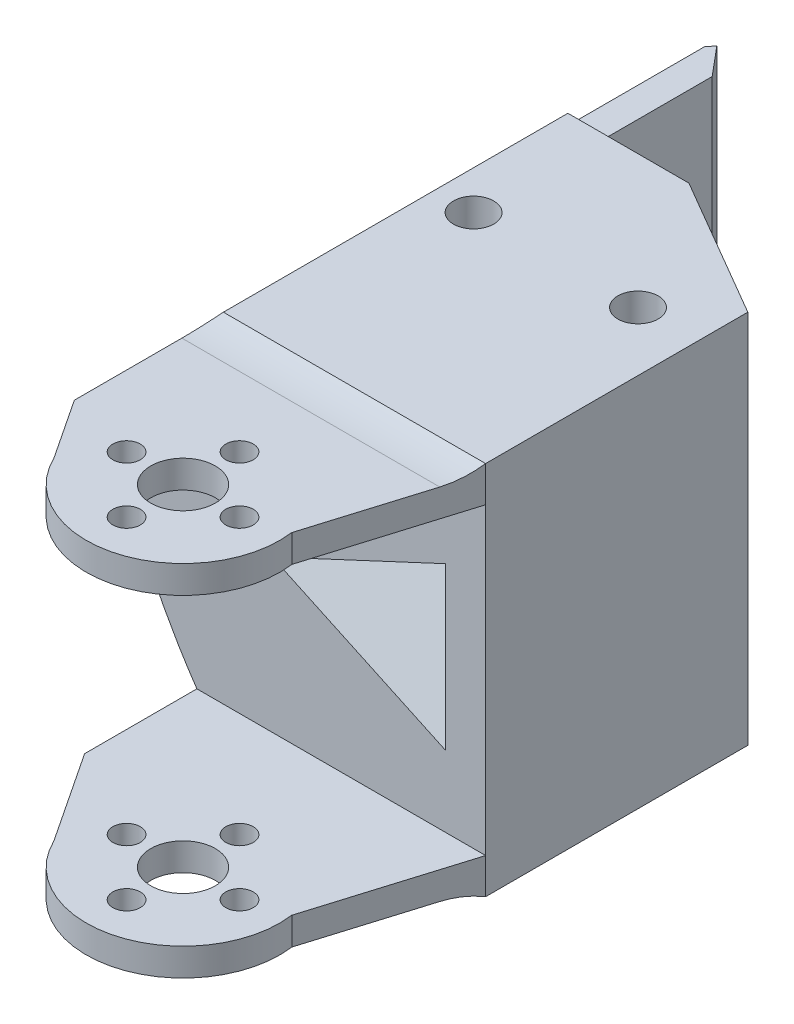
SolidWorks part; units mm, degrees
ref_plane "Front Plane" through (0, 0, 0) normal (0, 0, 1) x (1, 0, 0)
ref_plane "Top Plane" through (0, 0, 0) normal (0, 1, 0) x (1, 0, 0)
ref_plane "Right Plane" through (0, 0, 0) normal (1, 0, 0) x (0, 0, -1)
sketch "Sketch2" plane through (0, 0, 0) normal (0, 1, 0) x (1, 0, 0)
  line L0 (17.5, 0) -> (17.5, 37.7)
  line L1 (-15, 2.5) -> (15, 2.5)
  line L2 (-15, 2.5) -> (-15, 37.7)
  line L4 (15, 2.5) -> (15, 37.7)
  line L5 (17.5, 37.7) -> (15, 37.7)
  line L7 (-17.5, 37.7) -> (-17.5, 0)
  line L8 (-17.5, 0) -> (17.5, 0)
  line L10 (-17.5, 37.7) -> (-15, 37.7)
  point P4 (0, 2.5)
  point P12 (0, 0)
  dimension "D1" = 2.5
  dimension "D2" = 2.5
  dimension "D3" = 37.7
  dimension "D4" = 30
  dimension "D5" = 15
extrude "Boss-Extrude1" add sketch "Sketch2" along normal blind 32.5
sketch "Sketch4" plane through (0, 0, 0) normal (0, -1, 0) x (1, 0, 0)
  line L0 (-17.5, 0) -> (-17.5, -7.4438)
  line L8 (17.5, -7.4438) -> (17.5, 0)
  line L9 (17.5, 0) -> (-17.5, 0)
  line L10 (17.5, 0) -> (17.5, -37.7) construction
  line L13 (-17.5, -7.4438) -> (-17.5, -37.7)
  line L23 (-17.5, -37.7) -> (-15, -37.7)
  line L34 (-15, -37.7) -> (-15, -7.5)
  line L35 (-15, -2.5) -> (-15, -37.7) construction
  line L36 (-15, -7.5) -> (15, -7.5)
  line L37 (15, -37.7) -> (15, -2.5) construction
  line L38 (15, -7.5) -> (15, -37.7)
  line L39 (15, -37.7) -> (17.5, -37.7)
  line L40 (17.5, -37.7) -> (17.5, -7.4438)
  circle A2 centre (-10.1889, -4.95) radius 1.05
  circle A5 centre (10.1889, -4.95) radius 1.05
  dimension "D5" = 2.1
  dimension "D1" = 7.5
  dimension "D6" = 7.3111
  dimension "D7" = 4.95
  dimension "D8" = 7.3111
extrude "Boss-Extrude2" add sketch "Sketch4" along normal blind 2
sketch "Sketch7" plane through (0, -2, 0) normal (0, -1, 0) x (1, 0, 0)
  line L0 (-17.5, 0) -> (-17.5, -37.7)
  line L1 (-17.5, -37.7) -> (-15, -37.7)
  line L2 (-17.5, 0) -> (17.5, 0)
  line L4 (17.5, 0) -> (17.5, -37.7)
  line L5 (17.5, -37.7) -> (15, -37.7)
  line L6 (15, -37.7) -> (15, -7.5)
  line L7 (15, -7.5) -> (-15, -7.5)
  line L8 (-15, -7.5) -> (-15, -37.7)
  circle A2 centre (-10.1889, -4.95) radius 2.495
  circle A3 centre (10.1889, -4.95) radius 2.495
  dimension "D1" = 4.99
extrude "Wire spacing2" add sketch "Sketch7" along normal blind 3
sketch "Sketch8" plane through (0, -5, 0) normal (0, -1, 0) x (1, 0, 0)
  line L0 (-17.5, 0) -> (-17.5, -37.7)
  line L1 (-17.5, -37.7) -> (17.5, -37.7)
  line L2 (17.5, -37.7) -> (17.5, 0) construction
  line L3 (15, -37.7) -> (17.5, -37.7) construction
  line L4 (-17.5, 0) -> (17.5, 0)
  line L6 (17.5, 0) -> (17.5, -37.7)
  circle A0 centre (-10.1889, -4.95) radius 2.495
  circle A1 centre (10.1889, -4.95) radius 2.495
  circle A2 centre (10.1889, -4.95) radius 2.495 construction
  circle A3 centre (-10.1889, -4.95) radius 2.495 construction
extrude "Boss-Extrude6" add sketch "Sketch8" along normal blind 2
sketch "Sketch5" plane through (0, 32.5, 0) normal (0, 1, 0) x (1, 0, 0)
  line L0 (-7.439, 10) -> (-7.439, 2.5)
  line L9 (15, 2.5) -> (-15, 2.5) construction
  line L11 (-10.1889, 12) -> (-7.439, 10)
  line L13 (-17.5, 0) -> (17.5, 0) construction
  line L15 (-17.5, 0) -> (-17.5, 37.7)
  line L17 (10.1889, 12) -> (7.439, 10)
  line L20 (17.5, 0) -> (17.5, 37.7)
  line L21 (-7.439, 2.5) -> (7.439, 2.5)
  line L22 (7.439, 2.5) -> (7.439, 10)
  line L23 (-17.5, 0) -> (17.5, 0)
  line L24 (-10.1889, 12) -> (-15, 12)
  line L25 (-15, 37.7) -> (-15, 7.5) construction
  line L26 (-15, 12) -> (-15, 37.7)
  line L27 (-15, 37.7) -> (-17.5, 37.7)
  line L30 (17.5, 37.7) -> (15, 37.7)
  line L31 (15, 37.7) -> (15, 12)
  line L32 (15, 7.5) -> (15, 37.7) construction
  line L33 (15, 12) -> (10.1889, 12)
  circle A0 centre (-10.1889, 4.95) radius 1.05 construction
  circle A1 centre (-10.1889, 8.7) radius 1.05
  circle A2 centre (10.1889, 8.7) radius 1.05
  circle A3 centre (10.1889, 4.95) radius 1.05 construction
  dimension "D4" = 0
  dimension "D7" = 8.7
  dimension "D3" = 0
  dimension "D1" = 12
  dimension "D2" = 10.061
  dimension "D5" = 10
  dimension "D6" = 10.061
extrude "Boss-Extrude3" add sketch "Sketch5" along normal blind 2
sketch "Sketch9" plane through (0, 34.5, 0) normal (0, 1, 0) x (1, 0, 0)
  line L0 (-17.5, 0) -> (-17.5, 37.7)
  line L1 (-17.5, 37.7) -> (-15, 37.7)
  line L2 (-15, 37.7) -> (-15, 12)
  line L3 (-15, 12) -> (-10.1889, 12)
  line L4 (-10.1889, 12) -> (-7.439, 10)
  line L5 (-7.439, 10) -> (-7.439, 2.5)
  line L6 (-7.439, 2.5) -> (7.439, 2.5)
  line L7 (7.439, 2.5) -> (7.439, 10)
  line L8 (7.439, 10) -> (10.1889, 12)
  line L9 (10.1889, 12) -> (7.439, 10) construction
  line L10 (10.1889, 12) -> (15, 12)
  line L11 (15, 7.5) -> (15, 37.7) construction
  line L12 (15, 12) -> (15, 37.7)
  line L13 (15, 37.7) -> (17.5, 37.7)
  line L14 (17.5, 0) -> (17.5, 37.7) construction
  line L15 (17.5, 37.7) -> (15, 37.7) construction
  line L16 (17.5, 37.7) -> (17.5, 0)
  line L17 (17.5, 0) -> (-17.5, 0)
  line L18 (15, 12) -> (10.1889, 12) construction
  circle A0 centre (-10.1889, 8.7) radius 2.495
  circle A1 centre (10.1889, 8.7) radius 2.495
  dimension "D1" = 4.99
  dimension "D2" = 0
extrude "Wire spacing1" add sketch "Sketch9" along normal blind 3
sketch "Sketch10" plane through (0, 37.5, 0) normal (0, 1, 0) x (1, 0, 0)
  line L1 (-17.5, 37.7) -> (17.5, 37.7)
  line L2 (-17.5, 37.7) -> (-17.5, 0)
  line L3 (-17.5, 0) -> (17.5, 0)
  line L4 (17.5, 37.7) -> (17.5, 0)
  circle A0 centre (-10.1889, 8.7) radius 2.495
  circle A1 centre (10.1889, 8.7) radius 2.495
  circle A2 centre (-10.1889, 8.7) radius 2.495 construction
  circle A3 centre (10.1889, 8.7) radius 2.495 construction
extrude "Boss-Extrude8" add sketch "Sketch10" along normal blind 2
sketch "Sketch11" plane through (0, 39.5, 0) normal (0, 1, 0) x (1, 0, 0)
  line L0 (17.5, 37.7) -> (-17.5, 37.7) construction
  circle A0 centre (0, 37.7) radius 12.5
  dimension "D1" = 25
extrude "Cut-Extrude1" cut sketch "Sketch11" against normal through all
sketch "Sketch12" plane through (0, -7, 0) normal (0, -1, 0) x (1, 0, 0)
  line L4 (0, -25.2) -> (17.5, -15)
  line L5 (17.5, -37.7) -> (17.5, 0) construction
  line L6 (17.5, -15) -> (17.5, -47.4845)
  line L7 (17.5, -47.4845) -> (0, -25.2)
  line L8 (17.5, 0) -> (-17.5, 0) construction
  arc A1 (12.5, -37.7) -> (-12.5, -37.7) centre (0, -37.7) ccw construction
  dimension "D1" = 15
extrude "Cut-Extrude2" cut sketch "Sketch12" against normal through all
sketch "Sketch13" plane through (0, 0, 0) normal (0, 0, 1) x (1, 0, 0)
  line L0 (17.5, -7) -> (-17.5, -7) construction
  line L1 (17.5, 39.5) -> (-27.5, 39.5)
  line L2 (17.5, 39.5) -> (17.5, -7)
  line L3 (17.5, -7) -> (-27.5, -7)
  line L4 (-27.5, 39.5) -> (-27.5, -7)
  line L5 (-17.5, 39.5) -> (-17.5, -7) construction
  dimension "D1" = 10
extrude "Boss-Extrude9" add sketch "Sketch13" along normal blind 17.5
sketch "Sketch15" plane through (0, 0, 0) normal (0, 0, -1) x (-1, 0, 0)
  line L0 (17.5, -7) -> (12.5, -7) construction
  line L1 (27.5, 39.5) -> (15, 39.5)
  line L2 (27.5, 39.5) -> (27.5, -7)
  line L3 (27.5, -7) -> (15, -7)
  line L4 (15, 39.5) -> (15, -7)
extrude "Boss-Extrude10" add sketch "Sketch15" along normal blind 50
sketch "Sketch18" plane through (0, -7, 0) normal (0, -1, 0) x (1, 0, 0)
  line L0 (12.5, 22.5) -> (12.5, 17.5)
  line L1 (12.5, 17.5) -> (-12.5, 17.5)
  line L2 (-12.5, 22.5) -> (-12.5, 17.5)
  line L3 (12.5, 22.5) -> (9.3675, 30)
  line L4 (-9.3675, 30) -> (-12.5, 22.5)
  line L5 (-27.5, 17.5) -> (17.5, 17.5) construction
  circle A0 centre (0, 37.5) radius 4
  arc A1 (9.3675, 30) -> (-9.3675, 30) centre (0, 37.5) ccw
  circle A2 centre (0, 30.5) radius 1.7
  circle A3 centre (-7, 37.5) radius 1.7
  circle A4 centre (0, 44.5) radius 1.7
  circle A5 centre (7, 37.5) radius 1.7
  point P11 (7.7726, 26.3901)
  point P12 (0, 17.5)
  point P21 (0, 49.5)
  dimension "D3" = 8
  dimension "D5" = 12
  dimension "D7" = 3.4
  dimension "D1" = 25
  dimension "D2" = 20
  dimension "D4" = 5
  dimension "D6" = 12.5
  dimension "D8" = 7
  dimension "D9" = 7
  dimension "D10" = 7
  dimension "D11" = 7
  dimension "D12" = 0
  dimension "D13" = 0
extrude "Boss-Extrude11" add sketch "Sketch18" against normal up to surface (46.5 mm away) up to face at (-8.1361, 39.5, -22.2514)
sketch "Sketch22" plane through (0, -7, 0) normal (0, -1, 0) x (1, 0, 0)
  line L0 (-27.5, 17.5) -> (-9, 45.4373)
  line L1 (-9, 45.4373) -> (-9, 17.5)
  line L2 (-9, 17.5) -> (-27.5, 17.5)
  line L4 (17.5, 17.5) -> (9, 45.4373)
  line L5 (9, 45.4373) -> (9, 17.5)
  line L6 (9, 17.5) -> (17.5, 17.5)
  arc A0 (9.3675, 30) -> (-9.3675, 30) centre (0, 37.5) ccw construction
  circle A1 centre (-7, 37.5) radius 1.7 construction
  circle A2 centre (7, 37.5) radius 1.7 construction
  dimension "D1" = 2
  dimension "D2" = 2
extrude "Boss-Extrude13" add sketch "Sketch22" against normal up to surface (46.5 mm away) up to face at (-4.6492, 39.5, -1.3222)
sketch "Sketch21" plane through (-27.5, 0, 0) normal (-1, 0, 0) x (0, 0, 1)
  line L1 (107.4125, 35.075) -> (17.5, 35.075)
  line L2 (107.4125, 35.075) -> (107.4125, -2.575)
  line L3 (107.4125, -2.575) -> (17.5, -2.575)
  line L4 (17.5, 35.075) -> (17.5, -2.575)
  line L6 (-50, -7) -> (-50, 39.5) construction
  line L7 (17.5, 39.5) -> (17.5, -7) construction
  point P6 (-50, 16.25)
  point P7 (17.5, 16.25)
  dimension "D1" = 37.65
  dimension "D2" = 0
extrude "Cut-Extrude3" cut sketch "Sketch21" against normal through all
sketch "Sketch26" plane through (0, 39.5, 0) normal (0, 1, 0) x (1, 0, 0)
  line L0 (-27.5, -17.5) -> (-27.5, 50) construction
  line L1 (-27.5, 29.3872) -> (-27.5, 50)
  line L2 (-27.5, 50) -> (-15, 50)
  spline S0 degree 2 poles (-15, 50) (-23.5947, 41.1535) (-27.5, 29.3872) knots 0 0 0 1 1 1
extrude "Cut-Extrude5" cut sketch "Sketch26" against normal through all
sketch "Sketch24" plane through (0, 0, 0) normal (0, 0, -1) x (-1, 0, 0)
  line L4 (15, -7) -> (27.5, -7)
  line L5 (27.5, -7) -> (27.5, 16.25)
  spline S0 degree 2 poles (27.5, 16.25) (23.3985, 3.4824) (15, -7) knots 0 0 0 1 1 1
extrude "Cut-Extrude4" cut sketch "Sketch24" against normal through all both and the other way through all
ref_plane "Plane1" through (0, 16.25, 0) normal (0, -1, 0) x (-1, 0, 0)
mirror "Mirror1" about plane through (0, 16.25, 0) normal (0, -1, 0) of "Cut-Extrude4"
sketch "Sketch27" plane through (0, 0, -2.5) normal (0, 0, -1) x (-1, 0, 0)
  line L0 (-12.5, 26.25) -> (8.9451, 16.25)
  line L1 (-17.875, 16.25) -> (17.875, 16.25) construction
  line L2 (8.9451, 16.25) -> (-12.5, 6.25)
  line L4 (-12.5, 6.25) -> (-12.5, 26.25)
  line L5 (-15, 32.5) -> (-15, 0) construction
  point P7 (-12.5, 16.25)
  dimension "D1" = 50
  dimension "D2" = 20
  dimension "D3" = 2.5
extrude "Cut-Extrude6" cut sketch "Sketch27" against normal through all
sketch "Sketch28" plane through (0, 39.5, 0) normal (0, 1, 0) x (1, 0, 0)
  line L0 (-15, 37.7) -> (-15, 50)
  line L1 (-15, 50) -> (-10, 50)
  line L2 (-10, 50) -> (-10, 47.127)
  line L3 (-10, 47.127) -> (-12.5, 47.127)
  line L4 (-12.5, 47.127) -> (-12.5, 37.7)
  line L5 (-15, 37.7) -> (-12.5, 37.7)
  dimension "D1" = 2.5
extrude "Boss-Extrude14" add sketch "Sketch28" against normal up to surface (46.5 mm away) up to face at (-0.7656, -7, 3.6462)
fillet "Fillet2" radius 10 1 edges at (-15, 16.25, -50)
sketch "Sketch29" plane through (0, 0, -37.7) normal (0, 0, 1) x (1, 0, 0)
  line L1 (-15, 37.5) -> (-12.5, 37.5)
  line L2 (-15, 37.5) -> (-15, -5)
  line L3 (-15, -5) -> (-12.5, -5)
  line L4 (-12.5, 37.5) -> (-12.5, -5)
extrude "Cut-Extrude8" cut sketch "Sketch29" against normal up to surface (9.427 mm away) up to face at (-11.25, 16.25, -47.127)
fillet "Fillet3" radius 1 1 edges at (-10, 16.25, -47.127)
sketch "Sketch33" plane through (0, 0, -50) normal (0, 0, -1) x (-1, 0, 0)
  line L1 (0, 39.5) -> (21.955, 39.5)
  line L2 (0, 39.5) -> (0, 34.5)
  line L3 (0, 34.5) -> (21.955, 34.5)
  line L4 (21.955, 39.5) -> (21.955, 34.5)
  line L5 (0, -7) -> (23.3737, -7)
  line L6 (0, -7) -> (0, -2)
  line L7 (0, -2) -> (23.3737, -2)
  line L8 (23.3737, -7) -> (23.3737, -2)
  dimension "D1" = 5
  dimension "D2" = 5
extrude "Cut-Extrude13" cut sketch "Sketch33" against normal up to vertex (24.8 mm away) up to point (0, 39.5, -25.2)
sketch "Sketch34" plane through (0, 34.5, 0) normal (0, 1, 0) x (1, 0, 0)
  line L0 (0, 25.2) -> (-17.9905, 46.6483)
  line L1 (-17.9905, 46.6483) -> (-19.0359, 53.4266)
  line L2 (-19.0359, 53.4266) -> (0, 53.4266)
  line L3 (0, 53.4266) -> (0, 25.2)
extrude "Cut-Extrude14" cut sketch "Sketch34" against normal through all both and the other way through all
sketch "Sketch36" plane through (17.5, 0, 0) normal (1, 0, 0) x (0, 0, -1)
  line L1 (-17.5, 39.5) -> (-49.5, 39.5)
  line L2 (-17.5, 39.5) -> (-17.5, 38.5)
  line L3 (-17.5, 38.5) -> (-49.5, 38.5)
  line L4 (-49.5, 39.5) -> (-49.5, 38.5)
  line L6 (-17.5, -7) -> (-49.5, -7)
  line L7 (-17.5, -7) -> (-17.5, -6)
  line L8 (-17.5, -6) -> (-49.5, -6)
  line L9 (-49.5, -7) -> (-49.5, -6)
  dimension "D1" = 1
extrude "Cut-Extrude15" cut sketch "Sketch36" against normal through all both and the other way through all
fillet "Fillet4" radius 10 2 edges at (0.8563, -6, 17.5) (0.8563, 38.5, 17.5)
sketch "Sketch37" plane through (0, 0, -2.5) normal (0, 0, -1) x (-1, 0, 0)
  line L0 (-15, 37.5) -> (-15, -5) construction
  line L1 (-15, 27.9049) -> (15, 27.9049)
  line L2 (-15, 27.9049) -> (-15, 4.6789)
  line L3 (-15, 4.6789) -> (15, 4.6789)
  line L4 (15, 27.9049) -> (15, 4.6789)
  line L5 (15, -2) -> (15, 34.5) construction
extrude "Cut-Extrude16" cut sketch "Sketch37" against normal blind 5 and the other way through all
sketch "Sketch38" plane through (0, 0, -2.5) normal (0, 0, -1) x (-1, 0, 0)
  line L1 (-7.439, 37.5) -> (7.439, 37.5)
  line L2 (-7.439, 37.5) -> (-7.439, -2.575)
  line L3 (-7.439, -2.575) -> (7.439, -2.575)
  line L4 (7.439, 37.5) -> (7.439, -2.575)
  line L8 (-17.5, -2.575) -> (18.2842, -2.575) construction
extrude "Cut-Extrude17" cut sketch "Sketch38" against normal blind 5
ref_axis "Axis1" through (0, 38.5, 37.5) along (0, -1, 0)
ref_axis "Axis2" through (7, 38.5, 37.5) along (0, -1, 0)
ref_axis "Axis3" through (0, 38.5, 44.5) along (0, -1, 0)
ref_plane "Plane2" through (0, 0, 0) normal (1, 0, 0) x (0, 0, -1)
ref_plane "Plane3" through (0, 0, 37.5) normal (0, 0, -1) x (-1, 0, 0)
ref_plane "Plane5" through (0, 16.25, 0) normal (0, 1, 0) x (1, 0, 0)
